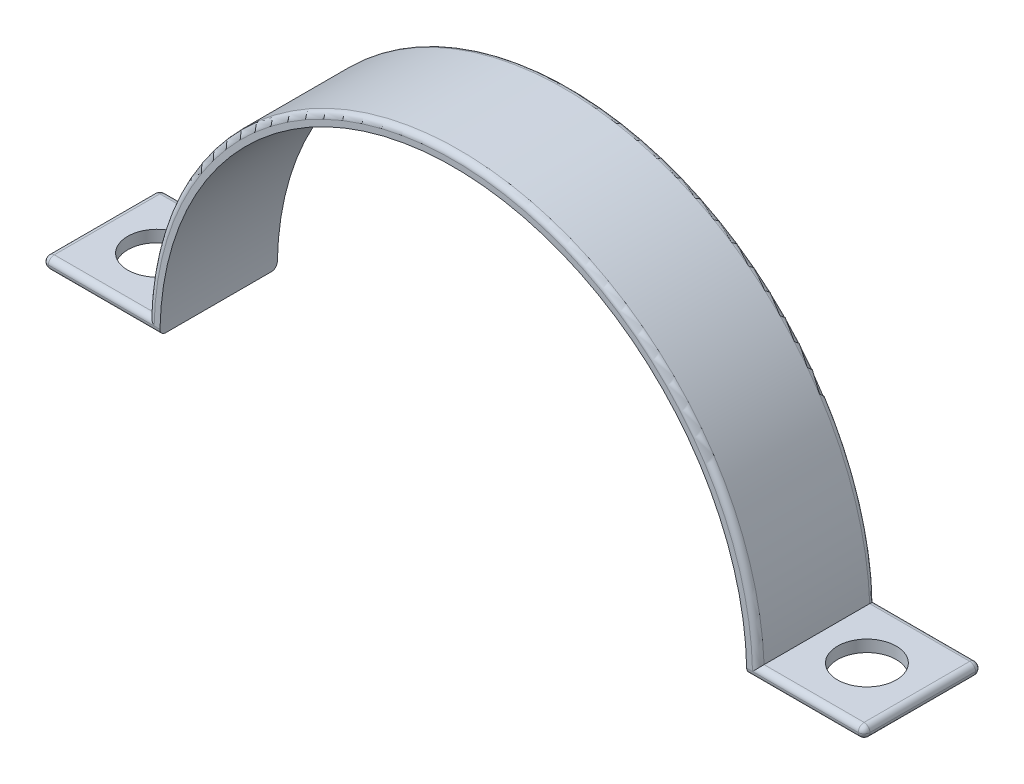
SolidWorks part; units mm, degrees
ref_plane "Front Plane" through (0, 0, 0) normal (0, 0, 1) x (1, 0, 0)
ref_plane "Top Plane" through (0, 0, 0) normal (0, 1, 0) x (1, 0, 0)
ref_plane "Right Plane" through (0, 0, 0) normal (1, 0, 0) x (0, 0, -1)
sketch "Sketch1" plane through (0, 0, 0) normal (0, 0, 1) x (1, 0, 0)
  line L0 (-50, 0) -> (-70, 0)
  line L1 (-70, 0) -> (-70, 2)
  line L2 (-70, 2) -> (-51.96, 2)
  line L4 (50, 0) -> (70, 0)
  line L5 (70, 0) -> (70, 2)
  line L6 (51.96, 2) -> (70, 2)
  arc A0 (50, 0) -> (-50, 0) centre (0, 0) ccw
  arc A1 (51.96, 2) -> (-51.96, 2) centre (0, 0) ccw
  dimension "D1" = 100
  dimension "D2" = 20
  dimension "D3" = 2
  dimension "D5" = 20
  dimension "D6" = 2
extrude "Boss-Extrude1" add sketch "Sketch1" along normal blind 20
fillet "Fillet4" radius 1 1 edges at (-70, 1, 20)
fillet "Fillet5" radius 1 1 edges at (-70, 1, 0)
fillet "Fillet7" radius 1 10 edges at (-59.5, 0, 20) (-69.7071, 0, 19.7071) (-59.5, 0, 0) (-69.7071, 0, 0.2929) (-60.48, 2, 20) (-69.7071, 2, 19.7071) (-60.48, 2, 0) (-69.7071, 2, 0.2929) (-70, 0, 10) (-70, 2, 10)
fillet "Fillet10" radius 1 2 edges at (70, 1, 20) (70, 1, 0)
fillet "Fillet11" radius 1 10 edges at (59.5, 0, 20) (69.7071, 0, 19.7071) (59.5, 0, 0) (69.7071, 0, 0.2929) (60.48, 2, 20) (69.7071, 2, 19.7071) (60.48, 2, 0) (69.7071, 2, 0.2929) (70, 0, 10) (70, 2, 10)
fillet "Fillet12" radius 1 2 edges at (0, 51.9985, 0) (0, 51.9985, 20)
sketch "Sketch2" plane through (0, 2, 0) normal (0, 1, 0) x (1, 0, 0)
  circle A0 centre (-60.48, -10) radius 5
  circle A1 centre (60.48, -10) radius 5
  dimension "D1" = 10
  dimension "D2" = 10
extrude "Cut-Extrude1" cut sketch "Sketch2" against normal through all
